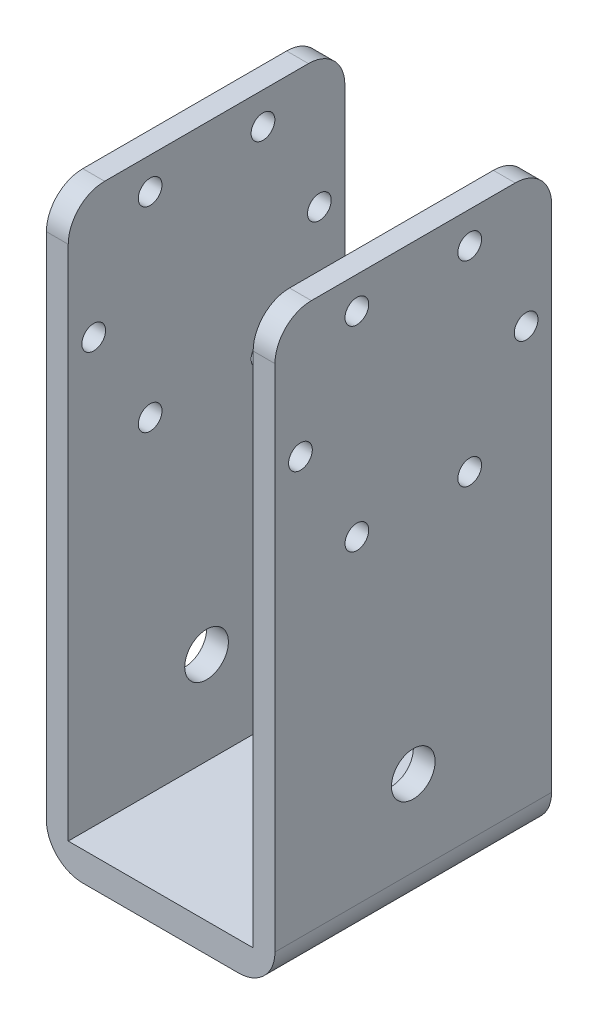
SolidWorks part; units mm, degrees
ref_plane "Front Plane" through (0, 0, 0) normal (0, 0, 1) x (1, 0, 0)
ref_plane "Top Plane" through (0, 0, 0) normal (0, 1, 0) x (1, 0, 0)
ref_plane "Right Plane" through (0, 0, 0) normal (1, 0, 0) x (0, 0, -1)
sketch "Sketch1" plane through (0, 0, 0) normal (0, 0, 1) x (1, 0, 0)
  line L0 (-15.7, 80) -> (-12.7, 80)
  line L1 (-12.7, 80) -> (-12.7, 4)
  line L2 (-12.7, 4) -> (12.7, 4)
  line L3 (-15.7, 80) -> (-15.7, 0)
  line L4 (-15.7, 0) -> (15.7, 0)
  line L5 (0, 33.2714) -> (0, -36.0595) construction
  line L6 (15.7, 80) -> (15.7, 0)
  line L7 (12.7, 80) -> (12.7, 4)
  line L8 (15.7, 80) -> (12.7, 80)
  point P11 (0, 0)
  point P13 (0, 4)
  dimension "D1" = 12.7
  dimension "D2" = 4
  dimension "D3" = 3
  dimension "D4" = 80
extrude "Boss-Extrude1" add sketch "Sketch1" along normal mid plane 38
sketch "Sketch2" plane through (15.7, 0, 0) normal (1, 0, 0) x (0, 0, -1)
  line L0 (0, 43.2613) -> (0, -4.7877) construction
  line L1 (-7.75, 75.63) -> (7.75, 75.63) construction
  line L2 (-19, 80) -> (19, 80) construction
  circle A0 centre (-7.75, 75.63) radius 1.63
  circle A1 centre (7.75, 75.63) radius 1.63
  circle A2 centre (-15.5, 62.2) radius 1.63
  circle A3 centre (15.5, 62.2) radius 1.63
  circle A4 centre (-7.75, 48.77) radius 1.63
  circle A5 centre (7.75, 48.77) radius 1.63
  point P7 (0, 75.63)
  dimension "D2" = 3.26
  dimension "D1" = 15.5
  dimension "D3" = 4.37
  dimension "D4" = 13.43
  dimension "D5" = 7.75
  dimension "D6" = 13.43
extrude "Cut-Extrude1" cut sketch "Sketch2" against normal through all
fillet "Fillet1" radius 5 6 edges at (-15.7, 0, 0) (15.7, 0, 0) (-14.2, 80, 19) (-14.2, 80, -19) (14.2, 80, -19) (14.2, 80, 19)
sketch "Sketch3" plane through (0, 4, 0) normal (0, 1, 0) x (1, 0, 0)
  line L0 (0, 25.1826) -> (0, -29.3208) construction
  line L1 (-12, 10) -> (-12, -10) construction
  circle A0 centre (-12, 10) radius 1.5
  circle A1 centre (-12, -10) radius 1.5
  circle A2 centre (12, -10) radius 1.5
  circle A3 centre (12, 10) radius 1.5
  point P4 (-12, 0)
  dimension "D3" = 3
  dimension "D1" = 12
  dimension "D2" = 10
extrude "Cut-Extrude2" [suppressed] cut sketch "Sketch3" against normal through all
sketch "Sketch4" plane through (15.7, 0, 0) normal (1, 0, 0) x (0, 0, -1)
  line L0 (-19, 4) -> (19, 4) construction
  circle A0 centre (0, 16.7) radius 3
  point P2 (0, 0)
  dimension "D1" = 6
  dimension "D2" = 12.7
extrude "Cut-Extrude3" cut sketch "Sketch4" against normal through all
